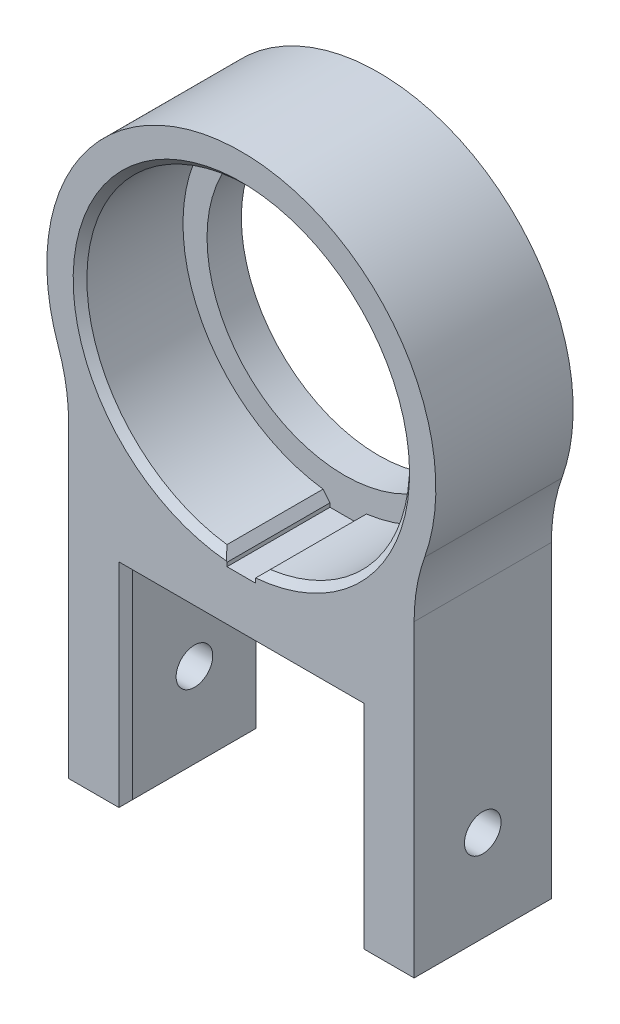
SolidWorks part; units mm, degrees
ref_plane "Front Plane" through (0, 0, 0) normal (0, 0, 1) x (1, 0, 0)
ref_plane "Top Plane" through (0, 0, 0) normal (0, 1, 0) x (1, 0, 0)
ref_plane "Right Plane" through (0, 0, 0) normal (1, 0, 0) x (0, 0, -1)
sketch "Sketch1" plane through (0, 0, 0) normal (0, 0, 1) x (1, 0, 0)
  line L1 (-15.1, -38) -> (-10.1, -38)
  line L2 (-10.1, -38) -> (-10.1, -20)
  line L3 (-10.1, -20) -> (10.1, -20)
  line L4 (10.1, -20) -> (10.1, -38)
  line L5 (10.1, -38) -> (15.1, -38)
  line L7 (55, 0) -> (-55, 0) construction
  line L8 (0, -44.7868) -> (0, 44.7868) construction
  line L9 (-15.1, -38) -> (-15.1, -11.0295)
  line L10 (15.1, -38) -> (15.1, -11.0295)
  circle A0 centre (0, 0) radius 12
  arc A2 (-16.0201, -5.6882) -> (16.0201, -5.6882) centre (0, 0) cw
  arc A3 (-16.0201, -5.6882) -> (-15.1, -11.0295) centre (-31.0633, -11.0295) cw
  arc A4 (15.1, -11.0295) -> (16.0201, -5.6882) centre (31.0633, -11.0295) cw
  dimension "D1" = 24
  dimension "D2" = 17
  dimension "D3" = 20
  dimension "D4" = 18
  dimension "D5" = 10.1
  dimension "D6" = 5
  dimension "D7" = 10.1
extrude "Boss-Extrude1" add sketch "Sketch1" along normal blind 12
sketch "Sketch9" plane through (0, 0, 12) normal (0, 0, 1) x (1, 0, 0)
  circle A0 centre (0, 0) radius 14.1
  dimension "D1" = 28.2
extrude "Cut-Extrude2" cut sketch "Sketch9" against normal offset from surface (9 mm away) 3 up to face at (0, -20.2669, 0)
ref_plane "Plane1" through (0, 20, 0) normal (0, 1, 0) x (1, 0, 0)
sketch "Sketch7" plane through (0, 0, 0) normal (0, 0, 1) x (1, 0, 0)
  circle A0 centre (0, 0) radius 14
  circle A1 centre (0, 0) radius 12
  dimension "D1" = 28
  dimension "D2" = 24
extrude "Boss-Extrude3" add sketch "Sketch7" along normal blind 3
sketch "Sketch12" plane through (10.1, 0, 0) normal (-1, 0, 0) x (0, 0, 1)
  line L0 (12, -11.0295) -> (12, -38) construction
  line L2 (12, -20) -> (0, -20) construction
  circle A0 centre (6, -30) radius 1.6
  dimension "D1" = 3.2
  dimension "D2" = 6
  dimension "D3" = 10
extrude "Cut-Extrude5" cut sketch "Sketch12" against normal through all both and the other way through all
sketch "Sketch13" plane through (0, 0, 12) normal (0, 0, 1) x (1, 0, 0)
  line L0 (0, -44.7868) -> (0, 44.7868) construction
  line L1 (-1.25, -15.0445) -> (1.25, -15.0445)
  line L2 (-1.25, -15.0445) -> (-1.25, -14.0445)
  line L3 (-1.25, -14.0445) -> (1.25, -14.0445)
  line L4 (1.25, -15.0445) -> (1.25, -14.0445)
  line L5 (-1.25, -15.0445) -> (1.25, -14.0445) construction
  line L6 (-1.25, -14.0445) -> (1.25, -15.0445) construction
  circle A0 centre (0, 0) radius 14.1 construction
  point P0 (0, -14.5445)
  dimension "D1" = 1
  dimension "D2" = 2.5
extrude "Cut-Extrude6" cut sketch "Sketch13" against normal up to surface (9 mm away) up to face at (-12, 0, 3)
chamfer "Chamfer1" distance 0.6 angle 45 11 edges at (0, 14.1, 12) (-10.1, -29, 0) (0, -20, 0) (10.1, -29, 0) (10.1, -38, 6) (-10.1, -38, 6) (-10.1, -29, 12) (0, -20, 12) (10.1, -29, 12) (-1.25, -14.0445, 7.5) (1.25, -14.0445, 7.5)
